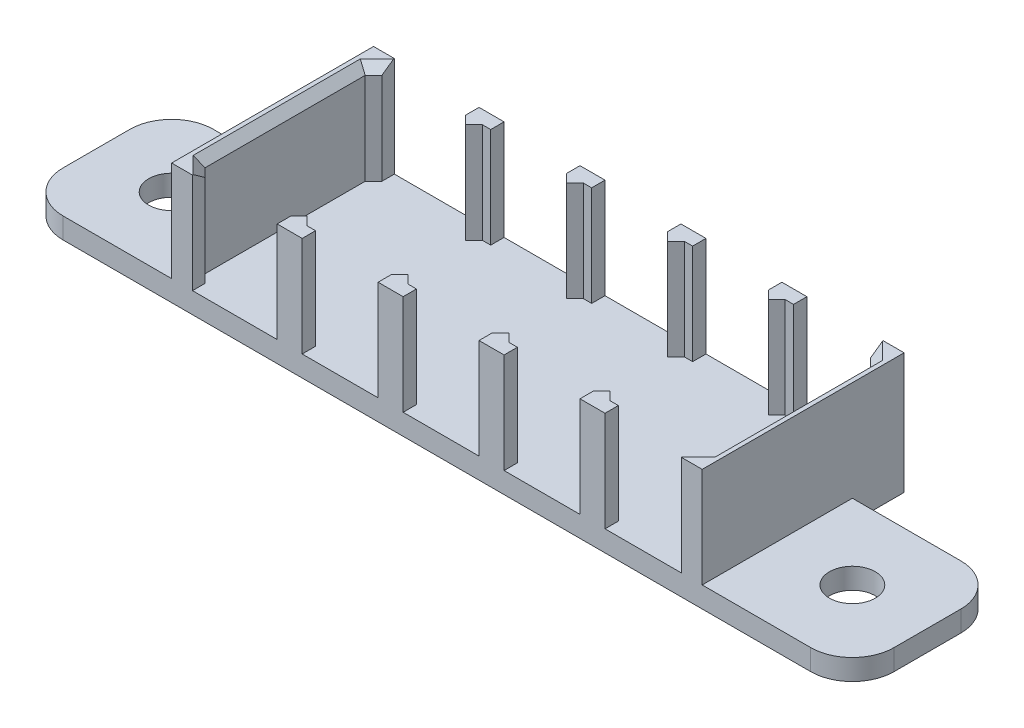
SolidWorks part; units mm, degrees
ref_plane "Спереди" through (0, 0, 0) normal (0, 0, 1) x (1, 0, 0)
ref_plane "Сверху" through (0, 0, 0) normal (0, 1, 0) x (1, 0, 0)
ref_plane "Справа" through (0, 0, 0) normal (1, 0, 0) x (0, 0, -1)
sketch "Эскиз1" plane through (0, 0, 0) normal (0, 1, 0) x (1, 0, 0)
  line L0 (0, 0) -> (0, 14.4286) construction
  line L1 (31.8, 14.4286) -> (31.8, -9.7714)
  line L2 (31.8, 14.4286) -> (-31.8, 14.4286)
  line L4 (31.8, -9.7714) -> (-31.8, -9.7714)
  line L5 (-31.8, 14.4286) -> (-31.8, -9.7714)
  point P7 (0, -9.7714)
  dimension "D1" = 31.8
  dimension "D2" = 24.2
extrude "Бобышка-Вытянуть1" add sketch "Эскиз1" along normal blind 2.5
sketch "Эскиз2" plane through (0, 0, 0) normal (0, 1, 0) x (1, 0, 0)
  line L0 (-31.8, 8.2286) -> (-49.8, -9.7714) construction
  line L1 (-31.8, -9.7714) -> (-44.8, -9.7714)
  line L2 (-31.8, -9.7714) -> (-31.8, 8.2286)
  line L3 (-31.8, 8.2286) -> (-44.8, 8.2286)
  line L4 (-49.8, -4.7714) -> (-49.8, 3.2286)
  arc A0 (-44.8, -9.7714) -> (-49.8, -4.7714) centre (-44.8, -4.7714) cw
  arc A1 (-49.8, 3.2286) -> (-44.8, 8.2286) centre (-44.8, 3.2286) cw
  circle A3 centre (-40.8, -0.7714) radius 2.75
  point P7 (-49.8, -9.7714)
  point P10 (-49.8, 8.2286)
  dimension "D3" = 5
  dimension "D4" = 5.5
  dimension "D1" = 18
  dimension "D2" = 18
extrude "Бобышка-Вытянуть2" add sketch "Эскиз2" along normal blind 2.5
mirror "Зеркальное отражение1" about plane through (0, 0, 0) normal (1, 0, 0) of "Бобышка-Вытянуть2"
sketch "Эскиз3" plane through (0, 2.5, 0) normal (0, 1, 0) x (1, 0, 0)
  line L1 (-31.8, 14.4286) -> (-30.3, 14.4286)
  line L2 (-31.8, 14.4286) -> (-31.8, -9.7714)
  line L5 (-30.3, 14.4286) -> (-29.3, 14.4286)
  line L6 (31.8, 14.4286) -> (-31.8, 14.4286) construction
  line L7 (-29.3, 14.4286) -> (-29.3, 12.9286)
  line L8 (-29.3, 12.9286) -> (-30.3, 11.9286)
  line L9 (-30.3, 14.4286) -> (-30.3, 13.0893) construction
  line L13 (-31, 2.3286) -> (-31.8, 2.3286) construction
  line L14 (-31.8, -9.7714) -> (-30.3, -9.7714)
  line L15 (-30.3, -9.7714) -> (-29.3, -9.7714)
  line L16 (-29.3, -8.2714) -> (-30.3, -7.2714)
  line L17 (-29.3, -9.7714) -> (-29.3, -8.2714)
  line L18 (-30.3, 11.9286) -> (-30.3, -7.2714)
  dimension "D1" = 1.5
  dimension "D2" = 1.5
  dimension "D3" = 1
  dimension "D4" = 135
  dimension "D5" = 24.2
extrude "Бобышка-Вытянуть3" add sketch "Эскиз3" along normal blind 12
mirror "Зеркальное отражение2" about plane through (0, 0, 0) normal (1, 0, 0) of "Бобышка-Вытянуть3"
chamfer "Фаска1" distance 1 angle 45 6 edges at (-29.8, 14.5, -12.4286) (29.8, 14.5, -12.4286) (-29.8, 14.5, 7.7714) (-30.3, 14.5, -2.3286) (29.8, 14.5, 7.7714) (30.3, 14.5, -2.3286)
sketch "Эскиз4" plane through (0, 2.5, 0) normal (0, 1, 0) x (1, 0, 0)
  line L0 (-30.3, -17.4714) -> (-30.3, -9.7714) construction
  line L2 (-30.3, -9.7714) -> (-18.15, -9.7714) construction
  line L4 (-18.15, -9.7714) -> (-19.15, -9.7714)
  line L5 (-19.15, -9.7714) -> (-19.15, -8.1714)
  line L6 (-19.15, -8.1714) -> (-18.15, -8.1714) construction
  line L7 (-18.15, -8.1714) -> (-18.15, -7.1714) construction
  line L8 (-19.15, -8.1714) -> (-18.15, -7.1714)
  line L9 (-18.15, -8.1714) -> (-17.15, -8.1714) construction
  line L10 (-18.15, -7.1714) -> (-17.15, -8.1714)
  line L11 (-17.15, -8.1714) -> (-16.15, -8.1714)
  line L12 (-16.15, -8.1714) -> (-16.15, -9.7714)
  line L13 (-16.15, -9.7714) -> (-18.15, -9.7714)
  line L14 (-44.8, -9.7714) -> (-31.8, -9.7714) construction
  line L16 (-30.3, -7.2714) -> (-30.3, 11.9286) construction
  dimension "D1" = 12.15
  dimension "D2" = 1
  dimension "D3" = 1.6
  dimension "D4" = 1
  dimension "D5" = 1
  dimension "D6" = 1
  dimension "D7" = 1
extrude "Бобышка-Вытянуть4" add sketch "Эскиз4" along normal blind 12
ref_plane "Плоскость1" through (0, 0, -2.3286) normal (0, 0, 1) x (1, 0, 0)
mirror "Зеркальное отражение3" about plane through (0, 0, -2.3286) normal (0, 0, 1) of "Бобышка-Вытянуть4"
pattern_linear "Линейный массив1" count 4 spacing 12.1 along (1, 0, 0) of "Зеркальное отражение3"
